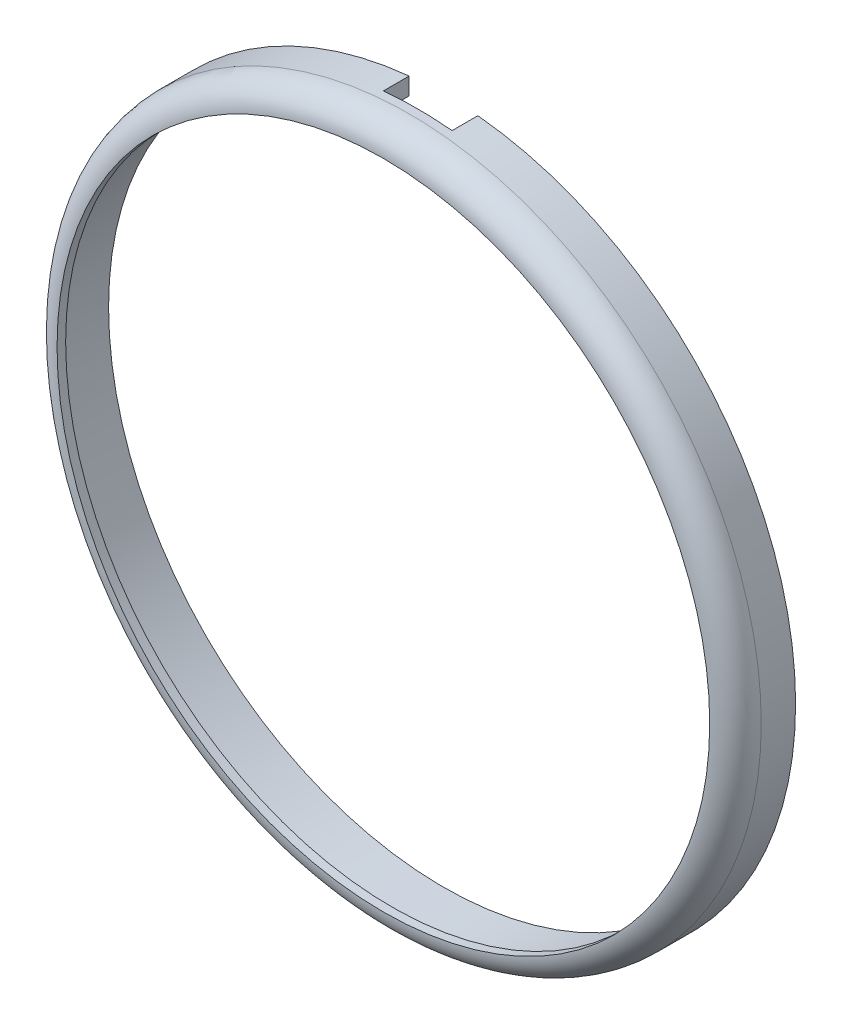
SolidWorks part; units mm, degrees
ref_plane "Front Plane" through (0, 0, 0) normal (0, 0, 1) x (1, 0, 0)
ref_plane "Top Plane" through (0, 0, 0) normal (0, 1, 0) x (1, 0, 0)
ref_plane "Right Plane" through (0, 0, 0) normal (1, 0, 0) x (0, 0, -1)
sketch "Croquis1" plane through (0, 0, 0) normal (0, 0, 1) x (1, 0, 0)
  circle A0 centre (0, 0) radius 20.5
  dimension "D1" = 41
extrude "Saliente-Extruir1" add sketch "Croquis1" along normal blind 3.5
ref_plane "Plano1" through (0, 20, 0) normal (0, 1, 0) x (-1, 0, 0)
sketch "Croquis3" plane through (0, 20, 0) normal (0, 1, 0) x (-1, 0, 0)
  line L0 (-2, 0) -> (2, 0)
  line L1 (2, 0) -> (2, 1.5)
  line L2 (2, 1.5) -> (-2, 1.5)
  line L3 (-2, 1.5) -> (-2, 0)
  dimension "D1" = 4
  dimension "D2" = 1.5
extrude "Cortar-Extruir2" cut sketch "Croquis3" along normal blind 3 and the other way blind 10
sketch "Croquis4" plane through (0, 0, 0) normal (0, 0, -1) x (-1, 0, 0)
  circle A0 centre (0, 0) radius 19.5
  dimension "D1" = 39
extrude "Cortar-Extruir3" cut sketch "Croquis4" against normal blind 3
sketch "Croquis5" plane through (0, 0, 3) normal (0, 0, -1) x (-1, 0, 0)
  circle A0 centre (0, 0) radius 19
  dimension "D1" = 38
extrude "Cortar-Extruir4" cut sketch "Croquis5" against normal blind 3
fillet "Redondeo1" radius 1.5 1 edges at (20.5, 0, 3.5)
